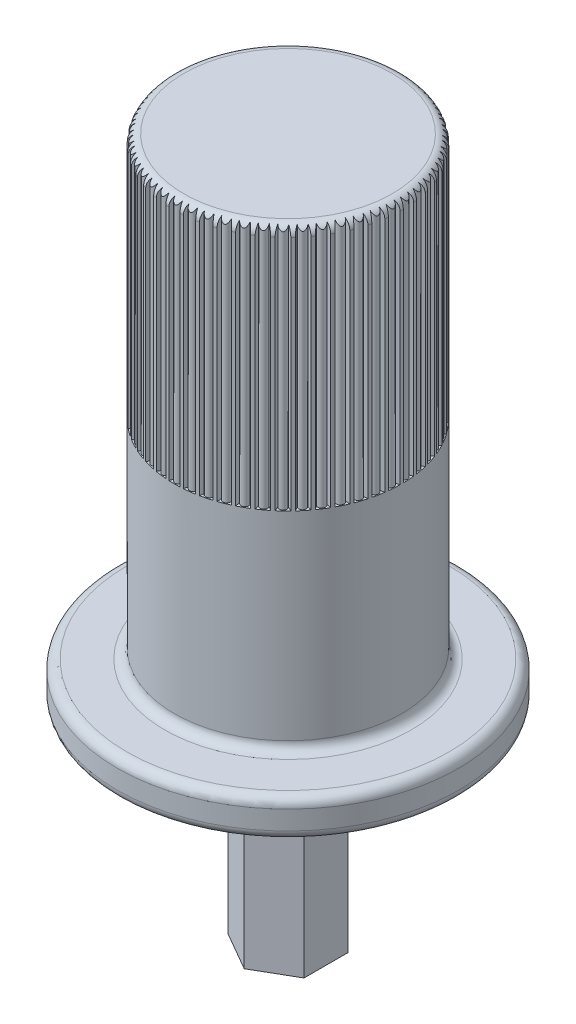
SolidWorks part; units mm, degrees
material "ABS"
ref_plane "Front" through (0, 0, 0) normal (0, 0, 1) x (1, 0, 0)
ref_plane "Top" through (0, 0, 0) normal (0, 1, 0) x (1, 0, 0)
ref_plane "Right" through (0, 0, 0) normal (1, 0, 0) x (0, 0, -1)
sketch "Sketch1" plane through (0, 0, 0) normal (0, 0, 1) x (1, 0, 0)
  line L0 (0, 0) -> (0, 13)
  line L1 (0, 13) -> (-3, 13)
  line L2 (-3, 13) -> (-3, 1)
  line L3 (-3, 1) -> (-4.5, 1)
  line L4 (-4.5, 1) -> (-4.5, 0)
  line L5 (-4.5, 0) -> (0, 0)
  dimension "D1" = 4.5
  dimension "D2" = 3
  dimension "D3" = 1
  dimension "D4" = 13
revolve "Revolve1" add sketch "Sketch1" angle 360 about L0
fillet "Fillet1" radius 0.25 1 edges at (0, 13, -3)
sketch "Sketch2" plane through (0, 13, 0) normal (0, 1, 0) x (1, 0, 0)
  line L0 (-0.1, 2.8733) -> (-0.25, 3.2733)
  line L1 (-0.25, 3.2733) -> (0.25, 3.2733)
  line L2 (0.25, 3.2733) -> (0.1, 2.8733)
  circle A0 centre (0, 0) radius 2.875 construction
  arc A1 (-0.1, 2.8733) -> (0.1, 2.8733) centre (0, 2.875) cw
  dimension "D1" = 0.1
  dimension "D2" = 5.75
  dimension "D3" = 0.5
  dimension "D4" = 0.4
extrude "Cut-Extrude1" cut sketch "Sketch2" against normal blind 6.5
pattern_circular "CirPattern1" count 50 over 360 about axis through (0, 0, 0) along (0, -1, 0) of "Cut-Extrude1"
fillet "Fillet2" radius 0.25 3 edges at (0, 0, -4.5) (0, 1, -3) (0, 1, -4.5)
sketch "Sketch3" plane through (0, 0, 0) normal (0, 1, 0) x (1, 0, 0)
  line L1 (0, 1.1547) -> (-1, 0.5774)
  line L2 (-1, 0.5774) -> (-1, -0.5774)
  line L3 (-1, -0.5774) -> (0, -1.1547)
  line L4 (0, -1.1547) -> (1, -0.5774)
  line L5 (1, -0.5774) -> (1, 0.5774)
  line L6 (1, 0.5774) -> (0, 1.1547)
  circle A0 centre (0, 0) radius 1 construction
  dimension "D1" = 2
extrude "Boss-Extrude1" add sketch "Sketch3" against normal blind 5.5
